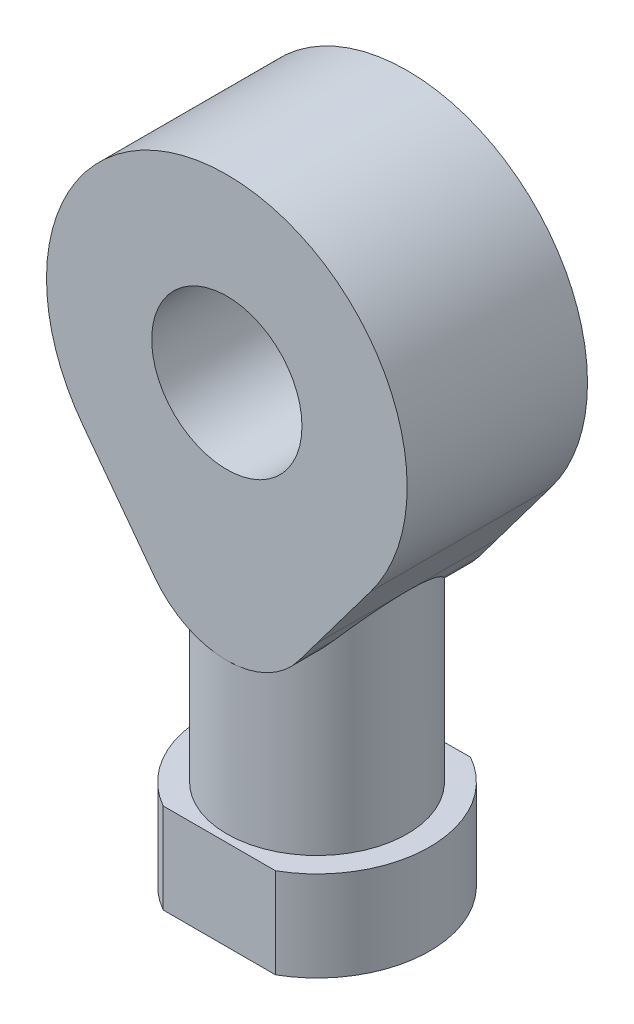
SolidWorks part; units mm, degrees
ref_plane "Front Plane" through (0, 0, 0) normal (0, 0, 1) x (1, 0, 0)
ref_plane "Top Plane" through (0, 0, 0) normal (0, 1, 0) x (1, 0, 0)
ref_plane "Right Plane" through (0, 0, 0) normal (1, 0, 0) x (0, 0, -1)
sketch "Sketch2" plane through (0, 0, 0) normal (0, 1, 0) x (1, 0, 0)
  line L0 (-3.8054, 6.4629) -> (3.6775, 6.5365)
  line L1 (-3.7417, -6.5) -> (3.7417, -6.5)
  arc A0 (-3.8054, 6.4629) -> (-3.7417, -6.5) centre (0, 0) ccw
  arc A1 (3.7417, -6.5) -> (3.6775, 6.5365) centre (0, 0) ccw
  dimension "D1" = 15
  dimension "D2" = 6.5
  dimension "D3" = 7.483
  dimension "D4" = 6.5
extrude "Boss-Extrude1" add sketch "Sketch2" along normal blind 6
sketch "Sketch3" plane through (0, 6, 0) normal (0, 1, 0) x (1, 0, 0)
  circle A0 centre (0, 0) radius 6
  dimension "D1" = 12
extrude "Boss-Extrude2" add sketch "Sketch3" along normal blind 14
sketch "Sketch4" plane through (0, 0, 0) normal (0, 0, 1) x (1, 0, 0)
  line L0 (6, 20) -> (-6, 20) construction
  line L1 (6, 20) -> (9.5518, 24.736)
  line L2 (-6, 20) -> (-9.5515, 24.736)
  line L3 (-6, 20) -> (-4.8001, 18.4)
  line L4 (4.8001, 18.4) -> (6, 20)
  arc A0 (9.5518, 24.736) -> (-9.5515, 24.736) centre (0.0002, 32) ccw
  arc A1 (4.8001, 18.4) -> (-4.8001, 18.4) centre (0, 21.9999) cw
  dimension "D2" = 24
  dimension "D3" = 6
  dimension "D1" = 12
extrude "Boss-Extrude3" add sketch "Sketch4" along normal blind 6 and the other way blind 6
sketch "Sketch5" plane through (0, 0, 6) normal (0, 0, 1) x (1, 0, 0)
  circle A0 centre (0.0002, 32) radius 12 construction
  circle A1 centre (0.0002, 32) radius 5
  dimension "D1" = 32
  dimension "D2" = 10
extrude "Cut-Extrude1" cut sketch "Sketch5" against normal through all
sketch "Sketch6" plane through (0, 0, 0) normal (0, -1, 0) x (1, 0, 0)
  circle A0 centre (0, 0) radius 4.9
extrude "Cut-Extrude2" cut sketch "Sketch6" against normal blind 20
